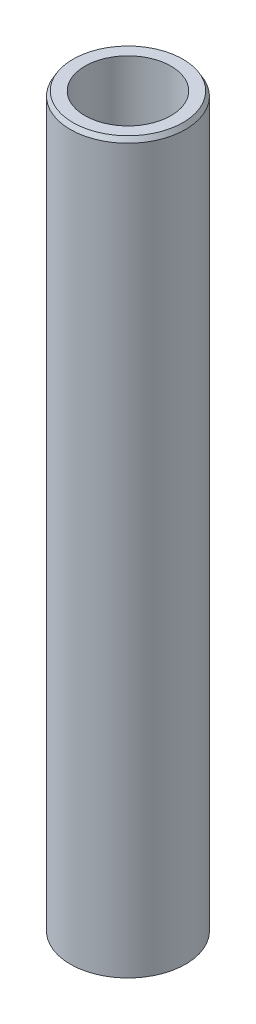
SolidWorks part; units mm, degrees
ref_plane "Front Plane" through (0, 0, 0) normal (0, 0, 1) x (1, 0, 0)
ref_plane "Top Plane" through (0, 0, 0) normal (0, 1, 0) x (1, 0, 0)
ref_plane "Right Plane" through (0, 0, 0) normal (1, 0, 0) x (0, 0, -1)
sketch "Sketch1" plane through (0, 0, 0) normal (0, 1, 0) x (1, 0, 0)
  circle A0 centre (0, 0) radius 12.5
  dimension "SHAFT_OD" = 25
extrude "Boss-Extrude1" add sketch "Sketch1" along normal blind 158.3559
sketch "Sketch2" plane through (0, 0, 0) normal (0, 1, 0) x (1, 0, 0)
  circle A0 centre (0, 0) radius 9.3227
  dimension "BORE_D" = 18.6453
extrude "Cut-Extrude1" cut sketch "Sketch2" along normal through all
chamfer "Chamfer1" distance 0.999 angle 30 2 edges at (0, 158.3559, 12.5) (0, 0, 12.5) first distance on face at (0, 158.3559, 12.5) first distance on face at (0, 0, 9.3227)
